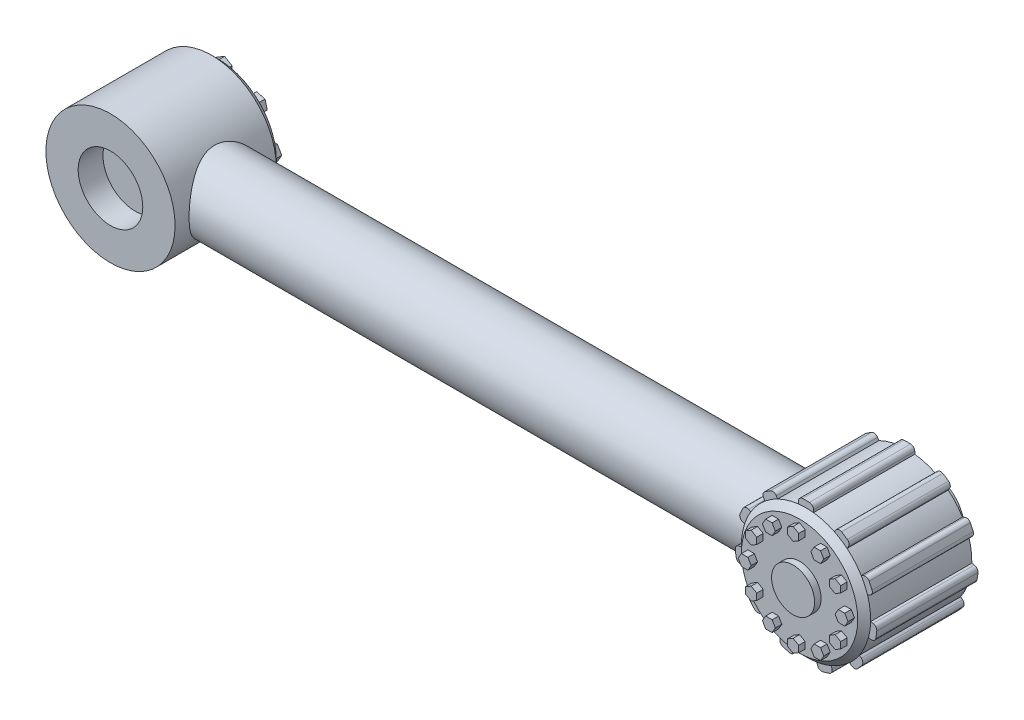
SolidWorks part; units mm, degrees
ref_plane "Ön Düzlem" through (0, 0, 0) normal (0, 0, 1) x (1, 0, 0)
ref_plane "Üst Düzlem" through (0, 0, 0) normal (0, 1, 0) x (1, 0, 0)
ref_plane "Sağ Düzlem" through (0, 0, 0) normal (1, 0, 0) x (0, 0, -1)
sketch "Sketch1" plane through (0, 0, 0) normal (0, 0, 1) x (1, 0, 0)
  line L0 (-160, 0) -> (160, 0) construction
  line L1 (0, 86.5625) -> (0, -84.5015) construction
  line L2 (156.5, 29.7951) -> (156.5, 30.9637)
  line L3 (163.5, 29.7951) -> (163.5, 30.9637)
  line L4 (179.0529, 23.173) -> (179.6846, 24.1561)
  line L5 (160, -30) -> (160, 30) construction
  line L6 (173.1641, 26.9575) -> (173.7958, 27.9406)
  line L7 (188.5566, 9.1936) -> (189.6195, 9.6791)
  line L8 (185.6487, 15.5611) -> (186.7116, 16.0465)
  line L9 (188.9938, -7.7047) -> (190.1504, -7.871)
  line L10 (189.99, -0.7759) -> (191.1466, -0.9422)
  line L11 (180.2256, -22.1568) -> (181.1088, -22.922)
  line L12 (184.8097, -16.8665) -> (185.6928, -17.6318)
  line L13 (165.036, -29.5743) -> (165.3653, -30.6955)
  line L14 (171.7525, -27.6022) -> (172.0817, -28.7234)
  line L15 (148.2475, -27.6022) -> (147.9183, -28.7234)
  line L16 (154.964, -29.5743) -> (154.6347, -30.6955)
  line L17 (135.1903, -16.8665) -> (134.3072, -17.6318)
  line L18 (139.7744, -22.1568) -> (138.8912, -22.922)
  line L19 (130.01, -0.7759) -> (128.8534, -0.9422)
  line L20 (131.0062, -7.7047) -> (129.8496, -7.871)
  line L21 (134.3513, 15.5611) -> (133.2884, 16.0465)
  line L22 (131.4434, 9.1936) -> (130.3805, 9.6791)
  line L23 (146.8359, 26.9575) -> (146.2042, 27.9406)
  line L24 (140.9471, 23.173) -> (140.3154, 24.1561)
  arc A0 (140.9471, 23.173) -> (134.3513, 15.5611) centre (160, 0) ccw
  circle A1 centre (160, 0) radius 33 construction
  arc A2 (158.4032, 32.9613) -> (161.5968, 32.9613) centre (160, 0) cw
  arc A3 (163.5, 30.9637) -> (161.5968, 32.9613) centre (161.5, 30.9637) ccw
  arc A4 (158.4032, 32.9613) -> (156.5, 30.9637) centre (158.5, 30.9637) ccw
  arc A5 (176.477, 28.5921) -> (173.7958, 27.9406) centre (175.4784, 26.8593) ccw
  arc A6 (176.477, 28.5921) -> (179.1635, 26.8656) centre (160, 0) cw
  arc A7 (179.6846, 24.1561) -> (179.1635, 26.8656) centre (178.0021, 25.2374) ccw
  arc A8 (189.3194, 15.1451) -> (186.7116, 16.0465) centre (187.5424, 14.2272) ccw
  arc A9 (189.3194, 15.1451) -> (190.646, 12.2402) centre (160, 0) cw
  arc A10 (189.6195, 9.6791) -> (190.646, 12.2402) centre (188.7887, 11.4983) ccw
  arc A11 (192.8531, -3.1104) -> (191.1466, -0.9422) centre (190.862, -2.9219) ccw
  arc A12 (192.8531, -3.1104) -> (192.3986, -6.2714) centre (160, 0) cw
  arc A13 (190.1504, -7.871) -> (192.3986, -6.2714) centre (190.4351, -5.8913) ccw
  arc A14 (185.9562, -20.3783) -> (185.6928, -17.6318) centre (184.3831, -19.1433) ccw
  arc A15 (185.9562, -20.3783) -> (183.8649, -22.7919) centre (160, 0) cw
  arc A16 (181.1088, -22.922) -> (183.8649, -22.7919) centre (182.4185, -21.4105) ccw
  arc A17 (170.8184, -31.1763) -> (172.0817, -28.7234) centre (170.1627, -29.2868) ccw
  arc A18 (170.8184, -31.1763) -> (167.7542, -32.076) centre (160, 0) cw
  arc A19 (165.3653, -30.6955) -> (167.7542, -32.076) centre (167.2842, -30.132) ccw
  arc A20 (152.2458, -32.076) -> (154.6347, -30.6955) centre (152.7158, -30.132) ccw
  arc A21 (152.2458, -32.076) -> (149.1816, -31.1763) centre (160, 0) cw
  arc A22 (147.9183, -28.7234) -> (149.1816, -31.1763) centre (149.8373, -29.2868) ccw
  arc A23 (136.1351, -22.7919) -> (138.8912, -22.922) centre (137.5815, -21.4105) ccw
  arc A24 (136.1351, -22.7919) -> (134.0438, -20.3783) centre (160, 0) cw
  arc A25 (134.3072, -17.6318) -> (134.0438, -20.3783) centre (135.6169, -19.1433) ccw
  arc A26 (127.6014, -6.2714) -> (129.8496, -7.871) centre (129.5649, -5.8913) ccw
  arc A27 (127.6014, -6.2714) -> (127.1469, -3.1104) centre (160, 0) cw
  arc A28 (128.8534, -0.9422) -> (127.1469, -3.1104) centre (129.138, -2.9219) ccw
  arc A29 (129.354, 12.2402) -> (130.3805, 9.6791) centre (131.2113, 11.4983) ccw
  arc A30 (129.354, 12.2402) -> (130.6806, 15.1451) centre (160, 0) cw
  arc A31 (133.2884, 16.0465) -> (130.6806, 15.1451) centre (132.4576, 14.2272) ccw
  arc A32 (140.8365, 26.8656) -> (140.3154, 24.1561) centre (141.9979, 25.2374) ccw
  arc A33 (140.8365, 26.8656) -> (143.523, 28.5921) centre (160, 0) cw
  arc A34 (146.2042, 27.9406) -> (143.523, 28.5921) centre (144.5216, 26.8593) ccw
  arc A35 (156.5, 29.7951) -> (146.8359, 26.9575) centre (160, 0) ccw
  arc A36 (173.1641, 26.9575) -> (163.5, 29.7951) centre (160, 0) ccw
  arc A37 (185.6487, 15.5611) -> (179.0529, 23.173) centre (160, 0) ccw
  arc A38 (189.99, -0.7759) -> (188.5566, 9.1936) centre (160, 0) ccw
  arc A39 (184.8097, -16.8665) -> (188.9938, -7.7047) centre (160, 0) ccw
  arc A40 (171.7525, -27.6022) -> (180.2256, -22.1568) centre (160, 0) ccw
  arc A41 (154.964, -29.5743) -> (165.036, -29.5743) centre (160, 0) ccw
  arc A42 (139.7744, -22.1568) -> (148.2475, -27.6022) centre (160, 0) ccw
  arc A43 (131.0062, -7.7047) -> (135.1903, -16.8665) centre (160, 0) ccw
  arc A44 (131.4434, 9.1936) -> (130.01, -0.7759) centre (160, 0) ccw
  point P16 (163.5, 32.8139)
  point P19 (156.5, 32.8139)
  dimension "D2" = 60
  dimension "D3" = 66
  dimension "D5" = 2
  dimension "D1" = 320
  dimension "D4" = 3.5
  dimension "D6" = 11
extrude "Boss-Extrude2" add sketch "Sketch1" against normal blind 47 contours A39 L9 A13 A12 A11 L10 A38 L7 A10 A9 A8 L8 A37 L4 A7 A6 A5 L6 A36 L3 A3 A2 A4 L2 A35 L23 A34 A33 A32 L24 A0 L21 A31 A30 A29 L22 A44 L19 A28 A27 A26 L20 A43 L17 A25 A24 A23 L18 A42 L15 A22 A21 A20 L16 A41 L13 A19 A18 A17 L14 A40 L11 A16 A15 A14 L12
sketch "Sketch2" plane through (0, 0, 0) normal (0, 0, 1) x (1, 0, 0)
  circle A0 centre (160, 0) radius 30
  arc A1 (140.9471, 23.173) -> (134.3513, 15.5611) centre (160, 0) ccw construction
extrude "Boss-Extrude3" add sketch "Sketch2" along normal blind 3
chamfer "Chamfer1" distance 3 angle 45 1 edges at (190, 0, 3)
sketch "Sketch3" plane through (0, 0, 0) normal (0, 0, 1) x (1, 0, 0)
  line L0 (160, 0) -> (-160, 0) construction
  circle A0 centre (-160, 0) radius 30
  dimension "D1" = 60
  dimension "D2" = 320
extrude "Boss-Extrude4" add sketch "Sketch3" against normal blind 47 and the other way blind 3 separate body
chamfer "Chamfer2" distance 3 angle 45 1 edges at (-130, 0, -47)
sketch "Sketch4" plane through (0, 0, 3) normal (0, 0, 1) x (1, 0, 0)
  circle A0 centre (-160, 0) radius 15
  dimension "D1" = 30
extrude "Cut-Extrude1" cut sketch "Sketch4" against normal blind 11.5
sketch "Sketch5" plane through (0, 0, -47) normal (0, 0, -1) x (-1, 0, 0)
  circle A0 centre (-160, 0) radius 15
  dimension "D1" = 30
extrude "Boss-Extrude5" add sketch "Sketch5" along normal blind 11.5
sketch "Sketch6" plane through (0, 0, 0) normal (1, 0, 0) x (0, 0, -1)
  line L0 (-3, 27) -> (-3, -27) construction
  line L3 (0, 0) -> (21, 0) construction
  circle A0 centre (21, 0) radius 17.5
  dimension "D2" = 35
  dimension "D1" = 24
extrude "Boss-Extrude6" add sketch "Sketch6" along normal up to body (163.5 mm away) and the other way up to body contours A0
sketch "Sketch7" plane through (0, 0, -47) normal (0, 0, -1) x (-1, 0, 0)
  line L0 (160, 27) -> (160, -27) construction
  line L1 (133, 0) -> (187, 0) construction
  line L2 (178.7687, 18.7687) -> (174.8649, 19.8147)
  line L3 (160, 26.5429) -> (156.5, 24.5222)
  line L4 (156.5, 24.5222) -> (156.5, 20.4807)
  line L5 (156.5, 20.4807) -> (160, 18.46)
  line L6 (160, 18.46) -> (163.5, 20.4807)
  line L7 (163.5, 20.4807) -> (163.5, 24.5222)
  line L8 (163.5, 24.5222) -> (160, 26.5429)
  line L9 (174.8649, 19.8147) -> (172.0072, 16.9569)
  line L10 (172.0072, 16.9569) -> (173.0532, 13.0532)
  line L11 (173.0532, 13.0532) -> (176.9569, 12.0072)
  line L12 (176.9569, 12.0072) -> (179.8147, 14.8649)
  line L13 (179.8147, 14.8649) -> (178.7687, 18.7687)
  line L14 (186.5429, 0) -> (184.5222, 3.5)
  line L15 (184.5222, 3.5) -> (180.4807, 3.5)
  line L16 (180.4807, 3.5) -> (178.46, 0)
  line L17 (178.46, 0) -> (180.4807, -3.5)
  line L18 (180.4807, -3.5) -> (184.5222, -3.5)
  line L19 (184.5222, -3.5) -> (186.5429, 0)
  line L20 (178.7687, -18.7687) -> (179.8147, -14.8649)
  line L21 (179.8147, -14.8649) -> (176.9569, -12.0072)
  line L22 (176.9569, -12.0072) -> (173.0532, -13.0532)
  line L23 (173.0532, -13.0532) -> (172.0072, -16.9569)
  line L24 (172.0072, -16.9569) -> (174.8649, -19.8147)
  line L25 (174.8649, -19.8147) -> (178.7687, -18.7687)
  line L26 (160, -26.5429) -> (163.5, -24.5222)
  line L27 (163.5, -24.5222) -> (163.5, -20.4807)
  line L28 (163.5, -20.4807) -> (160, -18.46)
  line L29 (160, -18.46) -> (156.5, -20.4807)
  line L30 (156.5, -20.4807) -> (156.5, -24.5222)
  line L31 (156.5, -24.5222) -> (160, -26.5429)
  line L32 (141.2313, -18.7687) -> (145.1351, -19.8147)
  line L33 (145.1351, -19.8147) -> (147.9928, -16.9569)
  line L34 (147.9928, -16.9569) -> (146.9468, -13.0532)
  line L35 (146.9468, -13.0532) -> (143.0431, -12.0072)
  line L36 (143.0431, -12.0072) -> (140.1853, -14.8649)
  line L37 (140.1853, -14.8649) -> (141.2313, -18.7687)
  line L38 (133.4571, 0) -> (135.4778, -3.5)
  line L39 (135.4778, -3.5) -> (139.5193, -3.5)
  line L40 (139.5193, -3.5) -> (141.54, 0)
  line L41 (141.54, 0) -> (139.5193, 3.5)
  line L42 (139.5193, 3.5) -> (135.4778, 3.5)
  line L43 (135.4778, 3.5) -> (133.4571, 0)
  line L44 (141.2313, 18.7687) -> (140.1853, 14.8649)
  line L45 (140.1853, 14.8649) -> (143.0431, 12.0072)
  line L46 (143.0431, 12.0072) -> (146.9468, 13.0532)
  line L47 (146.9468, 13.0532) -> (147.9928, 16.9569)
  line L48 (147.9928, 16.9569) -> (145.1351, 19.8147)
  line L49 (145.1351, 19.8147) -> (141.2313, 18.7687)
  circle A0 centre (160, 0) radius 27 construction
  circle A1 centre (160, 22.5015) radius 3.5 construction
  circle A2 centre (160, 0) radius 10
  dimension "D4" = 20
  dimension "D1" = 7
  dimension "D2" = 18.46
  dimension "D3" = 8
extrude "Boss-Extrude7" add sketch "Sketch7" along normal blind 3
sketch "Sketch8" plane through (0, 0, 3) normal (0, 0, 1) x (1, 0, 0)
  line L0 (160, 27) -> (160, -27) construction
  line L1 (133, 0) -> (187, 0) construction
  line L2 (172.75, 22.0836) -> (169.75, 22.0836)
  line L3 (160, 25.5) -> (157.4019, 24)
  line L4 (157.4019, 24) -> (157.4019, 21)
  line L5 (157.4019, 21) -> (160, 19.5)
  line L6 (160, 19.5) -> (162.5981, 21)
  line L7 (162.5981, 21) -> (162.5981, 24)
  line L8 (162.5981, 24) -> (160, 25.5)
  line L9 (169.75, 22.0836) -> (168.25, 19.4856)
  line L10 (168.25, 19.4856) -> (169.75, 16.8875)
  line L11 (169.75, 16.8875) -> (172.75, 16.8875)
  line L12 (172.75, 16.8875) -> (174.25, 19.4856)
  line L13 (174.25, 19.4856) -> (172.75, 22.0836)
  line L14 (182.0836, 12.75) -> (179.4856, 14.25)
  line L15 (179.4856, 14.25) -> (176.8875, 12.75)
  line L16 (176.8875, 12.75) -> (176.8875, 9.75)
  line L17 (176.8875, 9.75) -> (179.4856, 8.25)
  line L18 (179.4856, 8.25) -> (182.0836, 9.75)
  line L19 (182.0836, 9.75) -> (182.0836, 12.75)
  line L20 (185.5, 0) -> (184, 2.5981)
  line L21 (184, 2.5981) -> (181, 2.5981)
  line L22 (181, 2.5981) -> (179.5, 0)
  line L23 (179.5, 0) -> (181, -2.5981)
  line L24 (181, -2.5981) -> (184, -2.5981)
  line L25 (184, -2.5981) -> (185.5, 0)
  line L26 (182.0836, -12.75) -> (182.0836, -9.75)
  line L27 (182.0836, -9.75) -> (179.4856, -8.25)
  line L28 (179.4856, -8.25) -> (176.8875, -9.75)
  line L29 (176.8875, -9.75) -> (176.8875, -12.75)
  line L30 (176.8875, -12.75) -> (179.4856, -14.25)
  line L31 (179.4856, -14.25) -> (182.0836, -12.75)
  line L32 (172.75, -22.0836) -> (174.25, -19.4856)
  line L33 (174.25, -19.4856) -> (172.75, -16.8875)
  line L34 (172.75, -16.8875) -> (169.75, -16.8875)
  line L35 (169.75, -16.8875) -> (168.25, -19.4856)
  line L36 (168.25, -19.4856) -> (169.75, -22.0836)
  line L37 (169.75, -22.0836) -> (172.75, -22.0836)
  line L38 (160, -25.5) -> (162.5981, -24)
  line L39 (162.5981, -24) -> (162.5981, -21)
  line L40 (162.5981, -21) -> (160, -19.5)
  line L41 (160, -19.5) -> (157.4019, -21)
  line L42 (157.4019, -21) -> (157.4019, -24)
  line L43 (157.4019, -24) -> (160, -25.5)
  line L44 (147.25, -22.0836) -> (150.25, -22.0836)
  line L45 (150.25, -22.0836) -> (151.75, -19.4856)
  line L46 (151.75, -19.4856) -> (150.25, -16.8875)
  line L47 (150.25, -16.8875) -> (147.25, -16.8875)
  line L48 (147.25, -16.8875) -> (145.75, -19.4856)
  line L49 (145.75, -19.4856) -> (147.25, -22.0836)
  line L50 (137.9164, -12.75) -> (140.5144, -14.25)
  line L51 (140.5144, -14.25) -> (143.1125, -12.75)
  line L52 (143.1125, -12.75) -> (143.1125, -9.75)
  line L53 (143.1125, -9.75) -> (140.5144, -8.25)
  line L54 (140.5144, -8.25) -> (137.9164, -9.75)
  line L55 (137.9164, -9.75) -> (137.9164, -12.75)
  line L56 (134.5, 0) -> (136, -2.5981)
  line L57 (136, -2.5981) -> (139, -2.5981)
  line L58 (139, -2.5981) -> (140.5, 0)
  line L59 (140.5, 0) -> (139, 2.5981)
  line L60 (139, 2.5981) -> (136, 2.5981)
  line L61 (136, 2.5981) -> (134.5, 0)
  line L62 (137.9164, 12.75) -> (137.9164, 9.75)
  line L63 (137.9164, 9.75) -> (140.5144, 8.25)
  line L64 (140.5144, 8.25) -> (143.1125, 9.75)
  line L65 (143.1125, 9.75) -> (143.1125, 12.75)
  line L66 (143.1125, 12.75) -> (140.5144, 14.25)
  line L67 (140.5144, 14.25) -> (137.9164, 12.75)
  line L68 (147.25, 22.0836) -> (145.75, 19.4856)
  line L69 (145.75, 19.4856) -> (147.25, 16.8875)
  line L70 (147.25, 16.8875) -> (150.25, 16.8875)
  line L71 (150.25, 16.8875) -> (151.75, 19.4856)
  line L72 (151.75, 19.4856) -> (150.25, 22.0836)
  line L73 (150.25, 22.0836) -> (147.25, 22.0836)
  circle A0 centre (160, 0) radius 27 construction
  circle A1 centre (160, 22.5) radius 2.5981 construction
  circle A2 centre (160, 0) radius 10
  dimension "D4" = 20
  dimension "D1" = 3
  dimension "D2" = 19.5
  dimension "D3" = 12
extrude "Boss-Extrude8" add sketch "Sketch8" along normal blind 3
